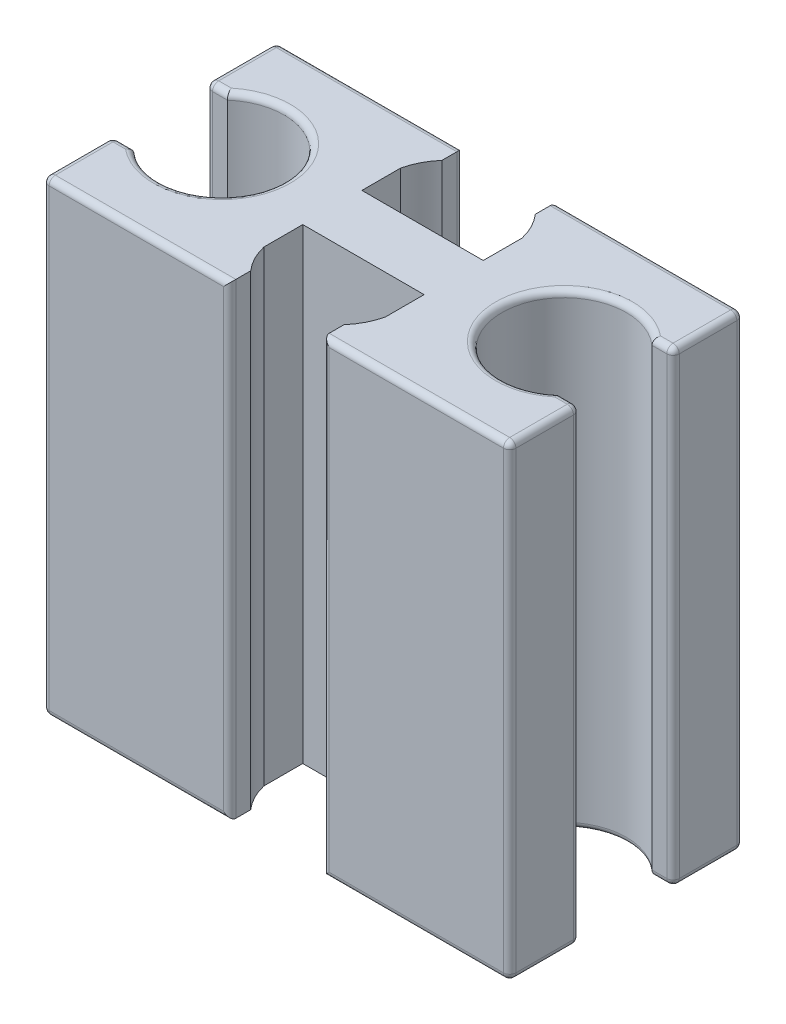
SolidWorks part; units mm, degrees
ref_plane "前视基准面" through (0, 0, 0) normal (0, 0, 1) x (1, 0, 0)
ref_plane "上视基准面" through (0, 0, 0) normal (0, 1, 0) x (1, 0, 0)
ref_plane "右视基准面" through (0, 0, 0) normal (1, 0, 0) x (0, 0, -1)
sketch "草图1" plane through (0, 0, 0) normal (0, 1, 0) x (1, 0, 0)
  line L0 (-1.5, 3.75) -> (-1.5, 3.0729)
  line L1 (-7.5, -3.75) -> (-1.5, -3.75)
  line L2 (-7.5, -3.75) -> (-7.5, -1.5)
  line L3 (-7.5, 3.75) -> (-1.5, 3.75)
  line L4 (7.5, -3.75) -> (7.5, -1.5)
  line L5 (1.5, 3.75) -> (1.5, 3.0729)
  line L6 (-1.95, 0.95) -> (1.95, 0.95)
  line L7 (-1.95, 0.95) -> (-1.95, 2.1944)
  line L8 (1.95, 2.1944) -> (1.95, 0.95)
  line L9 (1.5, 3.75) -> (7.5, 3.75)
  line L10 (-8.3526, 0) -> (8.2227, 0) construction
  line L11 (1.95, -2.1944) -> (1.95, -0.95)
  line L12 (-1.95, -0.95) -> (-1.95, -2.1944)
  line L13 (-1.95, -0.95) -> (1.95, -0.95)
  line L14 (1.5, -3.75) -> (1.5, -3.0729)
  line L15 (-1.5, -3.75) -> (-1.5, -3.0729)
  line L16 (1.5, -3.75) -> (7.5, -3.75)
  line L17 (0, 4.4094) -> (0, -4.5113) construction
  line L18 (-7.5, 1.5) -> (-6.8229, 1.5)
  line L19 (-7.5, -1.5) -> (-6.8229, -1.5)
  line L20 (-7.5, 1.5) -> (-7.5, 3.75)
  line L21 (7.5, 1.5) -> (6.8229, 1.5)
  line L22 (7.5, -1.5) -> (6.8229, -1.5)
  line L23 (7.5, 1.5) -> (7.5, 3.75)
  arc A0 (-1.5, 3.0729) -> (-1.95, 2.1944) centre (0, 1.75) ccw
  arc A1 (1.95, 2.1944) -> (1.5, 3.0729) centre (0, 1.75) ccw
  arc A2 (1.95, -2.1944) -> (1.5, -3.0729) centre (0, -1.75) cw
  arc A3 (-1.5, -3.0729) -> (-1.95, -2.1944) centre (0, -1.75) cw
  arc A4 (-6.8229, -1.5) -> (-6.8229, 1.5) centre (-5.5, 0) ccw
  arc A5 (6.8229, 1.5) -> (6.8229, -1.5) centre (5.5, 0) ccw
extrude "凸台-拉伸1" add sketch "草图1" along normal blind 15
fillet "圆角1" radius 0.2 28 edges at (-7.5, 7.5, 1.5) (-7.5, 15, 2.625) (-7.5, 0, 2.625) (-7.5, 15, -2.625) (-7.5, 7.5, -1.5) (-7.5, 0, -2.625) (-1.5, 7.5, -3.75) (-4.5, 15, -3.75) (-7.5, 7.5, -3.75) (-4.5, 0, -3.75) (4.5, 15, -3.75) (1.5, 7.5, -3.75) (4.5, 0, -3.75) (7.5, 7.5, -1.5) (7.5, 15, -2.625) (7.5, 7.5, -3.75) (7.5, 0, -2.625) (7.5, 15, 2.625) (7.5, 7.5, 1.5) (7.5, 0, 2.625) (-7.5, 7.5, 3.75) (-4.5, 15, 3.75) (-1.5, 7.5, 3.75) (-4.5, 0, 3.75) (1.5, 7.5, 3.75) (4.5, 15, 3.75) (7.5, 7.5, 3.75) (4.5, 0, 3.75)
fillet "圆角2" radius 0.2 20 edges at (-7.4414, 14.9414, 1.5586) (-7.4414, 14.9414, -1.5586) (7.4414, 14.9414, -1.5586) (7.4414, 14.9414, 1.5586) (-7.4414, 0.0586, 1.5586) (-7.4414, 0.0586, -1.5586) (7.4414, 0.0586, -1.5586) (7.4414, 0.0586, 1.5586) (-7.0614, 15, 1.5) (-3.5, 15, 0) (-7.0614, 15, -1.5) (7.0614, 15, -1.5) (7.0614, 15, 1.5) (3.5, 15, 0) (-7.0614, 0, 1.5) (-7.0614, 0, -1.5) (-3.5, 0, 0) (7.0614, 0, -1.5) (7.0614, 0, 1.5) (3.5, 0, 0)
